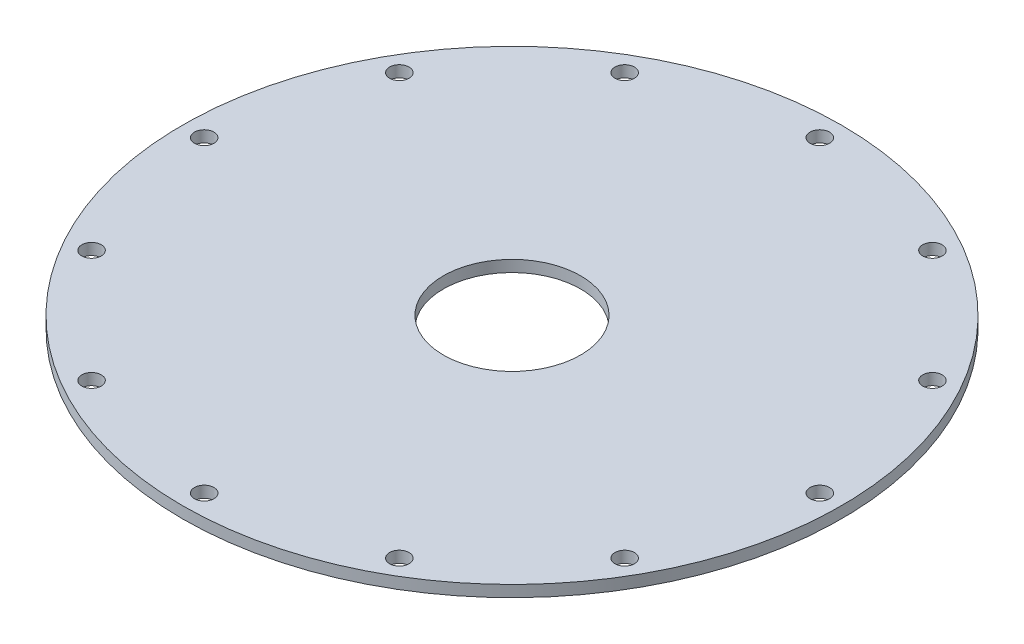
SolidWorks part; units mm, degrees
material "6063-T6"
ref_plane "Front Plane" through (0, 0, 0) normal (0, 0, 1) x (1, 0, 0)
ref_plane "Top Plane" through (0, 0, 0) normal (0, 1, 0) x (1, 0, 0)
ref_plane "Right Plane" through (0, 0, 0) normal (1, 0, 0) x (0, 0, -1)
ref_axis "Axis1" through (0, 55, 0) along (0, -1, 0)
sketch "Sketch1" plane through (0, 0, 0) normal (0, 0, 1) x (1, 0, 0)
  line L0 (-45.72, 0) -> (-9.525, 0)
  line L1 (0, 55) -> (0, -55) construction
  line L2 (-45.72, 0) -> (-45.72, 1.5875)
  line L3 (-45.72, 1.5875) -> (-9.525, 1.5875)
  line L4 (-45.72, 1.5875) -> (-9.525, 1.5875) construction
  line L5 (-9.525, 1.5875) -> (-9.525, 0)
  line L6 (-9.525, 0) -> (0, 0) construction
  line L7 (-45.72, 0) -> (-45.72, 1.5875) construction
  line L8 (-9.525, 1.5875) -> (-9.525, 0) construction
revolve "Revolve1" add sketch "Sketch1" angle 360 about axis through (0, 55, 0) along (0, -1, 0)
ref_plane "Hole Location Plane" through (0, 3.175, 0) normal (0, 1, 0) x (1, 0, 0)
sketch "Hole Location" plane through (0, 3.175, 0) normal (0, 1, 0) x (1, 0, 0)
  line L0 (0, 0) -> (-42.7006, 0) construction
  circle A0 centre (0, 0) radius 42.7006 construction
  dimension "D1" = 85.4012
hole_wizard "#36 (0.1065) Diameter Hole1" positions "Sketch4" profile "Sketch5" hole size "#36" standard "ANSI Inch" end condition through all
sketch "Sketch4" plane through (0, 1.5875, 0) normal (0, 1, 0) x (1, 0, 0)
  point P0 (-42.7006, 0)
sketch "Sketch5" plane through (-42.7006, 1.5875, 0) normal (1, 0, 0) x (0, 0, 1)
  line L0 (0, 0) -> (0, 1.5875)
  line L1 (0, 1.5875) -> (1.3525, 1.5875)
  line L2 (1.3525, 1.5875) -> (1.3525, 0)
  line L5 (1.3525, 0) -> (0, 0)
  line L11 (0, -6.35) -> (0, 107.95) construction
  dimension "Thru Hole Dia." = 2.7051
  dimension "Thru Hole Depth" = 1.5875
pattern_circular "CirPattern1" count 12 every 30 about axis through (0, 55, 0) along (0, -1, 0) of "#36 (0.1065) Diameter Hole1"
equation "\"D1@Hole Location\"=\"TANK DIAMETER@Cryo Tank.Assembly\"+\"GASKET SEAT THICKNESS@Cryo Tank.Assembly\"+\"LINER THICKNESS@Cryo Tank.Assembly\"+\"ALUMINUM LAP THICKNESS@Cryo Tank.Assembly\""
